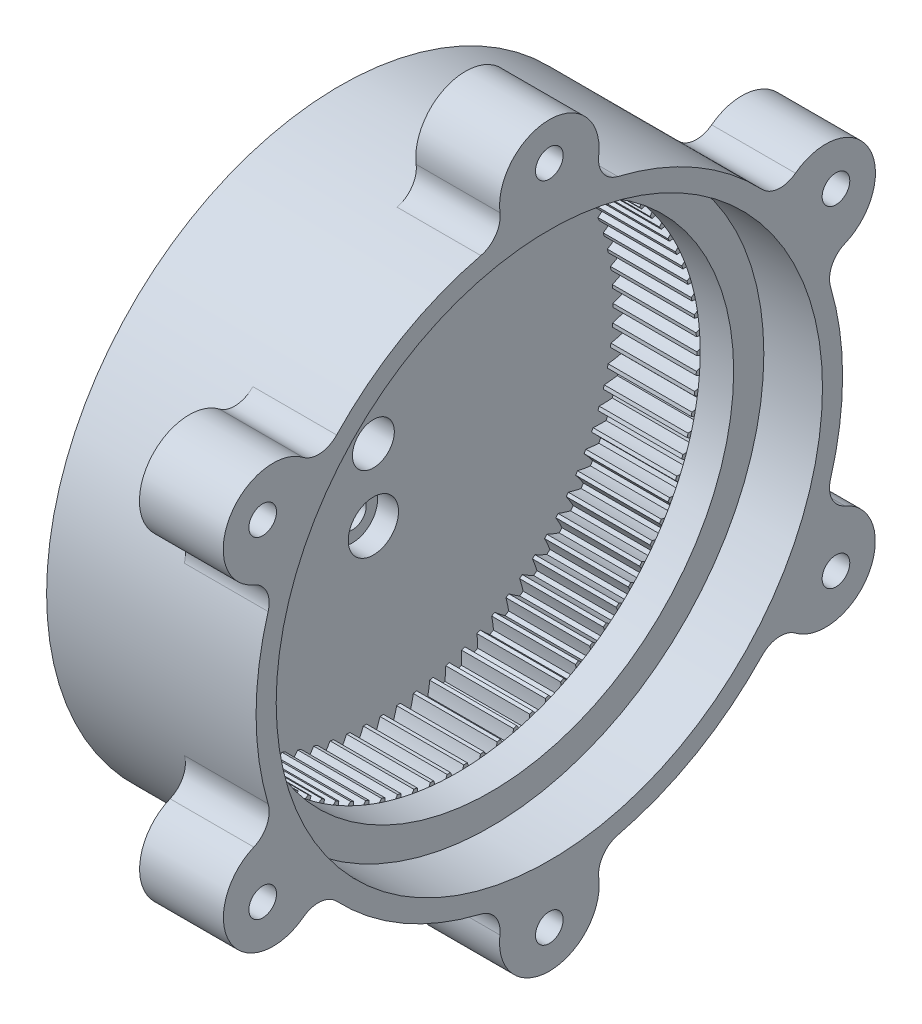
SolidWorks part; units mm, degrees
ref_plane "Plane1" through (0, 0, 0) normal (0, 0, 1) x (1, 0, 0)
ref_plane "Plane2" through (0, 0, 0) normal (0, 1, 0) x (1, 0, 0)
ref_plane "Plane3" through (0, 0, 0) normal (1, 0, 0) x (0, 0, -1)
sketch "HoldingSke" plane through (0, 0, 0) normal (0, 1, 0) x (1, 0, 0)
  line L0 (0, 0) -> (0, -1.5385)
  line L1 (-15, 0) -> (100, 0) construction
  line L2 (0, 0) -> (-2.1039, 2.3779)
  line L3 (0, 0) -> (-11.863, 4.5341)
  line L4 (0, 0) -> (0, 8.636)
  line L5 (0, 0) -> (-23.7986, -8.8762)
  line L6 (0, 0) -> (-10.5278, -7.1032)
  line L7 (-2.1039, 2.3779) -> (3.3635, 27.1825)
  line L8 (-76.2, 3.0279) -> (-54.61, 3.0279)
  line L9 (-71.009, 38.7566) -> (-53.1078, 45.2721)
  line L10 (-76.2, 71.12) -> (104.1128, 71.12)
  line L11 (0, 0) -> (-10, 0)
  line L12 (-76.2, 101.6) -> (-76.175, 101.6)
  line L13 (24.9733, 27.94) -> (52.9518, 28.4284)
  line L14 (24.9733, 27.94) -> (24.9743, 27.94)
  line L15 (24.9733, 27.94) -> (100.4006, 29.5858)
  circle A0 centre (0, 0) radius 35
  circle A1 centre (0, 0) radius 12.7
  circle A2 centre (0, 0) radius 12.7
  dimension "MHD" = 25.4
  dimension "Hub_dia" = 25.4
  dimension "Diameter" = 70
  dimension "Num_teeth" = 90
  dimension "Pitch" = 1.5385
  dimension "Overall_len" = 25.4
  dimension "Show_teeth" = 90
  dimension "Thickness" = 12.7
  dimension "OAL" = 25.4001
  dimension "T_dim" = 21.59
  dimension "Ap" = 20
  dimension "H" = 19.05
  dimension "Pitch_radius" = 180.3128
  dimension "Width" = 10
  dimension "Backlash" = 0.025
  dimension "Addendum_fac" = 1
  dimension "Dedendum_fac" = 1.25
  dimension "Clearance_fac" = 0.25
  dimension "Dedendum_add" = 0.001
  dimension "Module" = 0.65
sketch "BasProSke" plane through (0, 0, 0) normal (0, 1, 0) x (1, 0, 0)
  line L0 (-10, 0) -> (60, 0) construction
  line L1 (0, 28.6) -> (0, 35)
  line L2 (0, 28.6) -> (10, 28.6)
  line L3 (10, 28.6) -> (10, 35)
  line L4 (10, 35) -> (0, 35)
  dimension "Diameter" = 70
  dimension "Thickness" = 10
  dimension "Inside_diameter" = 57.2
revolve "Base-Revolve" add sketch "BasProSke" angle 360 about L0
sketch "TooCutSke" plane through (0, 0, 0) normal (1, 0, 0) x (0, 0, -1)
  line L3 (0.573, 29.2444) -> (0.573, 53.6633) construction
  line L4 (0, 0) -> (0, 59.563) construction
  line L5 (0, 0) -> (-2.3846, 68.2859) construction
  line L6 (-13.188, 24.292) -> (36.9564, 26.043) construction
  circle A0 centre (0, 0) radius 29.25 construction
  circle A1 centre (0, 0) radius 30.0635 construction
  circle A2 centre (0, 0) radius 24.7374 construction
  circle A3 centre (0, 0) radius 28.5746 construction
  arc A4 (0.7993, 28.5634) -> (0.2505, 30.0625) centre (-13.188, 24.292) ccw
  arc A5 (0.7993, 28.5634) -> (-0.7993, 28.5634) centre (0, 0) ccw
  arc A6 (0.2505, 30.0625) -> (-0.2505, 30.0625) centre (0, 0) ccw
  arc A7 (-0.2505, 30.0625) -> (-0.7993, 28.5634) centre (13.188, 24.292) ccw
  dimension "Pitch_dia" = 58.5
  dimension "Base_dia" = 49.4748
  dimension "Root_dia" = 60.127
  dimension "Overcut_dia" = 57.1492
  dimension "Flank_rad" = 14.625
  dimension "Half_ang" = 2
  dimension "Half_CT" = 0.573
extrude "ToothCut" cut sketch "TooCutSke" along normal through all
fillet "Breaks" [suppressed] radius 0.065
fillet "RootFillets" [suppressed] radius 0.1635
pattern_circular "TeethCuts" count 90 every 4 about axis through (-10, 0, 0) along (1, 0, 0) of "RootFillets", "Breaks", "ToothCut"
sketch "Sketch1" plane through (0, 0, 0) normal (-1, 0, 0) x (0, 0, 1)
  circle A0 centre (0, 0) radius 35
  dimension "D1" = 70
extrude "Boss-Extrude1" add sketch "Sketch1" along normal blind 4
sketch "Sketch2" plane through (-4, 0, 0) normal (-1, 0, 0) x (0, 0, 1)
  circle A0 centre (0, 0) radius 2.5
  dimension "D1" = 5
extrude "Cut-Extrude1" cut sketch "Sketch2" against normal blind 4
sketch "Sketch3" plane through (10, 0, 0) normal (1, 0, 0) x (0, 0, -1)
  circle A0 centre (0, 0) radius 29
  circle A1 centre (0, 0) radius 35
  dimension "D1" = 58
extrude "Boss-Extrude2" add sketch "Sketch3" along normal blind 4
sketch "Sketch4" plane through (14, 0, 0) normal (1, 0, 0) x (0, 0, -1)
  circle A0 centre (0, 0) radius 32.6
  circle A1 centre (0, 0) radius 35
  dimension "D1" = 65.2
extrude "Boss-Extrude3" add sketch "Sketch4" along normal blind 7
sketch "Sketch5" plane through (21, 0, 0) normal (1, 0, 0) x (0, 0, -1)
  line L2 (0, 0) -> (38.1051, 22) construction
  line L5 (0, 0) -> (27.5804, 21.5482) construction
  line L6 (0, 0) -> (32.4514, 13.1112) construction
  arc A0 (27.5804, 21.5482) -> (32.4514, 13.1112) centre (0, 0) cw
  circle A12 centre (0, 0) radius 35 construction
  arc A15 (4.8711, -34.6594) -> (-4.8711, -34.6594) centre (0, -38.0726) cw
  arc A19 (27.5804, 21.5482) -> (32.4514, 13.1112) centre (32.9718, 19.0363) cw
  arc A20 (4.8711, -34.6594) -> (-4.8711, -34.6594) centre (0, 0) cw
  arc A21 (-32.4514, 13.1112) -> (-27.5804, 21.5482) centre (-32.9718, 19.0363) cw
  arc A22 (-32.4514, 13.1112) -> (-27.5804, 21.5482) centre (0, 0) cw
  point P18 (0, 0)
  circle M5 centre (0, 0) radius 35
  dimension "D1" = 3
  dimension "D3" = 8
  dimension "D4" = 8
extrude "Boss-Extrude4" add sketch "Sketch5" against normal blind 10 contours M5 | A0 A19 | A21 A22 region at (21, -38.9929, 0)
sketch "Sketch8" plane through (21, 0, 0) normal (1, 0, 0) x (0, 0, -1)
  line L0 (0, 0) -> (34.208, 19.75) construction
  circle A0 centre (34.208, 19.75) radius 1.65
  circle A3 centre (0, -39.5) radius 1.65
  circle A4 centre (-34.208, 19.75) radius 1.65
  point P11 (0, 0)
  dimension "D2" = 3.3
  dimension "D1" = 39.5
extrude "Cut-Extrude2" cut sketch "Sketch8" against normal blind 10
sketch "Sketch9" plane through (21, 0, 0) normal (1, 0, 0) x (0, 0, -1)
  line L1 (0, 0) -> (38.1051, -22) construction
  line L4 (0, 0) -> (27.5804, -21.5482) construction
  line L5 (0, 0) -> (32.4514, -13.1112) construction
  arc A1 (27.5804, -21.5482) -> (32.4514, -13.1112) centre (0, 0) ccw
  arc A3 (-27.5804, -21.5482) -> (-32.4514, -13.1112) centre (-32.9597, -19.0293) cw
  arc A4 (-32.4514, -13.1112) -> (-27.5804, -21.5482) centre (0, 0) ccw
  arc A5 (32.4514, -13.1112) -> (27.5804, -21.5482) centre (32.9597, -19.0293) cw
  arc A6 (-4.8711, 34.6594) -> (4.8711, 34.6594) centre (0, 38.0585) cw
  arc A7 (4.8711, 34.6594) -> (-4.8711, 34.6594) centre (0, 0) ccw
  point P22 (0, 0)
  dimension "D4" = 8
  dimension "D5" = 8
  dimension "D6" = 3
extrude "Boss-Extrude5" add sketch "Sketch9" against normal blind 10 contours A5 A1 | A6 A7 | A3 A4
sketch "Sketch10" plane through (21, 0, 0) normal (1, 0, 0) x (0, 0, -1)
  line L1 (0, 0) -> (34.208, -19.75) construction
  circle A0 centre (34.208, -19.75) radius 1.65
  circle A1 centre (-34.208, -19.75) radius 1.65
  circle A2 centre (0, 39.5) radius 1.65
  dimension "D1" = 3.3
  dimension "D3" = 39.5
  dimension "D2" = 3
extrude "Cut-Extrude3" cut sketch "Sketch10" against normal blind 10
sketch "Sketch11" plane through (0, 0, 0) normal (1, 0, 0) x (0, 0, -1)
  line L0 (0, 0) -> (0, -8.5) construction
  line L1 (0, 0) -> (0, 8.5) construction
  circle A0 centre (0, -8.5) radius 1.65
  circle A1 centre (0, 8.5) radius 1.65
  dimension "D1" = 3.3
extrude "Cut-Extrude4" cut sketch "Sketch11" against normal through all
sketch "Sketch12" plane through (0, 0, 0) normal (1, 0, 0) x (0, 0, -1)
  circle A0 centre (0, 8.5) radius 3
  circle A1 centre (0, -8.5) radius 3
  dimension "D1" = 6
extrude "Cut-Extrude5" cut sketch "Sketch12" against normal blind 2.5
fillet "Fillet1" radius 3 12 edges at (16, -13.1112, -32.4514) (16, -21.5482, -27.5804) (16, -34.6594, 4.8711) (16, -34.6594, -4.8711) (16, -21.5482, 27.5804) (16, -13.1112, 32.4514) (16, 13.1112, 32.4514) (16, 21.5482, 27.5804) (16, 34.6594, 4.8711) (16, 34.6594, -4.8711) (16, 21.5482, -27.5804) (16, 13.1112, -32.4514)
equation "' \"Module@HoldingSke\" = 6.35"
equation "' \"Num_teeth@HoldingSke\" = 24"
equation "' \"Ap@HoldingSke\" =  14.5"
equation "' \"Ap@HoldingSke\" = 14.5"
equation "' \"Width@HoldingSke\" = 12"
equation "' \"Diameter@HoldingSke\" = 8 * 25.4"
equation "' \"Show_teeth@HoldingSke\" = 100"
equation "' \"Backlash@HoldingSke\" = 0.009 * 25.4"
equation "' \"Addendum_fac@HoldingSke\" = 1.0"
equation "' \"Dedendum_fac@HoldingSke\" = 1.25"
equation "' \"Dedendum_add@HoldingSke\" = 0.00005 * 25.4"
equation "' \"Clearance_fac@HoldingSke\" = 0.25"
equation "\"Pitch@HoldingSke\" = 1 / \"Module@HoldingSke\" "
equation "\"Overcut_dia@TooCutSke\" = (\"Num_teeth@HoldingSke\" - 2 * \"Addendum_fac@HoldingSke\") / \"Pitch@HoldingSke\" - 0.002 * 25.4"
equation "\"Pitch_dia@TooCutSke\" = \"Num_teeth@HoldingSke\" / \"Pitch@HoldingSke\""
equation "\"Base_dia@TooCutSke\" = \"Num_teeth@HoldingSke\" / \"Pitch@HoldingSke\" * cos((\"Ap@HoldingSke\"  * 3.14159265 / 180)) * 0.90"
equation "\"Root_dia@TooCutSke\" = \"Num_teeth@HoldingSke\"  / \"Pitch@HoldingSke\" + 2 *  \"Dedendum_fac@HoldingSke\"/ \"Pitch@HoldingSke\" + \"Dedendum_add@HoldingSke\" * 2"
equation "\"Half_ang@TooCutSke\" = 180 / \"Num_teeth@HoldingSke\""
equation "\"Half_CT@TooCutSke\" = \"Num_teeth@HoldingSke\" / \"Pitch@HoldingSke\" * sin((3.14159265 / 2 / \"Num_teeth@HoldingSke\")) / 2 + 10 * \"Backlash@HoldingSke\" / 4"
equation "\"Flank_rad@TooCutSke\" = \"Num_teeth@HoldingSke\" / \"Pitch@HoldingSke\" / 4"
equation "\"Radius@RootFillets\"= \"Clearance_fac@HoldingSke\" / \"Pitch@HoldingSke\" + \"Dedendum_add@HoldingSke\""
equation "\"Break_rad@Breaks\" = 0.02 / \"Pitch@HoldingSke\" * 5"
equation "\"Num_teeth@TeethCuts\" = int( \"Show_teeth@HoldingSke\" ) + 1"
equation "\"Num_teeth@TeethCuts\" = ((sgn( \"Num_teeth@TeethCuts\" - \"Num_teeth@HoldingSke\" )-1)*( \"Num_teeth@TeethCuts\" - \"Num_teeth@HoldingSke\" ))/-2+ \"Num_teeth@HoldingSke\""
equation "\"Num_teeth@TeethCuts\" = ((sgn( \"Num_teeth@TeethCuts\" - 2.0)+1)*( \"Num_teeth@TeethCuts\" - 2.0))/2 +2.0"
equation "\"Angle@TeethCuts\" = 360.0 / \"Num_teeth@HoldingSke\""
equation "\"Diameter@BasProSke\" = \"Num_teeth@HoldingSke\"  / \"Pitch@HoldingSke\" + 2 *  \"Dedendum_fac@HoldingSke\"/ \"Pitch@HoldingSke\" + \"Dedendum_add@HoldingSke\" * 2 + 0.002 * 25.4"
equation "\"Diameter@BasProSke\" = ((sgn( \"Diameter@BasProSke\"  - \"Diameter@HoldingSke\" )+1)*( \"Diameter@BasProSke\"  - \"Diameter@HoldingSke\" ))/2 + \"Diameter@HoldingSke\""
equation "\"Inside_diameter@BasProSke\" =  (\"Num_teeth@HoldingSke\" - 2 * \"Addendum_fac@HoldingSke\") / \"Pitch@HoldingSke\" "
equation "\"Thickness@BasProSke\"  = \"Width@HoldingSke\""
